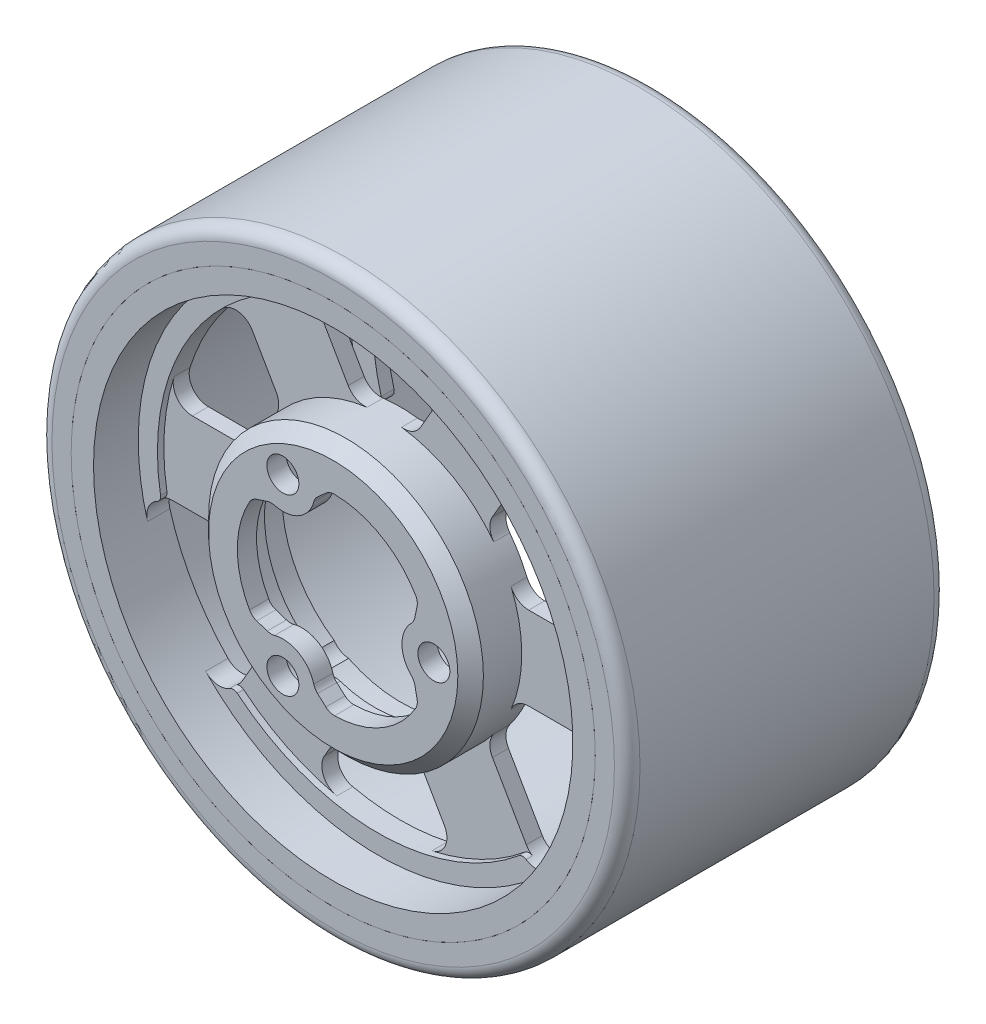
SolidWorks part; units mm, degrees
material "6061 合金"
ref_plane "前视基准面" through (0, 0, 0) normal (0, 0, 1) x (1, 0, 0)
ref_plane "上视基准面" through (0, 0, 0) normal (0, 1, 0) x (1, 0, 0)
ref_plane "右视基准面" through (0, 0, 0) normal (1, 0, 0) x (0, 0, -1)
sketch "草图1" plane through (0, 0, 0) normal (1, 0, 0) x (0, 0, -1)
  line L0 (0, 41) -> (-50, 41)
  line L6 (0, 71.4477) -> (0, 0) construction
  line L7 (0, 0) -> (-85.6485, 0) construction
  line L13 (0, 41) -> (0, 39)
  line L15 (-47, 9) -> (-50, 9)
  line L32 (-43.5, 18.5) -> (-43.5, 17.25)
  line L39 (-39.5, 39) -> (0, 39)
  line L43 (-39.5, 39) -> (-39.5, 18.5)
  line L44 (-50, 9) -> (-50, 21.5)
  line L46 (-43, 37.5) -> (-50, 37.5)
  line L52 (-42, 34.5) -> (-42, 21.5)
  line L53 (-43, 37.5) -> (-43, 34.5)
  line L54 (-43, 34.5) -> (-42, 34.5)
  line L57 (-43.5, 17.25) -> (-47, 17.25)
  line L58 (-47, 17.25) -> (-47, 9)
  line L59 (-39.5, 18.5) -> (-43.5, 18.5)
  line L60 (-42, 21.5) -> (-50, 21.5)
  line L61 (-50, 41) -> (-50, 37.5)
  dimension "D1" = 82
  dimension "D3" = 50
  dimension "D4" = 7
  dimension "D5" = 75
  dimension "D6" = 3
  dimension "D7" = 2.5
  dimension "D8" = 37
  dimension "D9" = 3
  dimension "D11" = 18
  dimension "D14" = 4
  dimension "D16" = 1.25
  dimension "D17" = 3.5
  dimension "D18" = 39
  dimension "D19" = 3
  dimension "D20" = 1
revolve "旋转1" add sketch "草图1" angle 360 about L7
sketch "草图15" plane through (0, 0, 0) normal (0, 1, 0) x (1, 0, 0)
  line L0 (0, 0) -> (50.0211, 0) construction
  line L1 (38.1, -6.35) -> (35.5, -6.35)
  line L2 (38.1, -6.35) -> (38.1, -8.35) construction
  line L3 (38.1, -8.35) -> (35.5, -8.35)
  line L4 (35.5, -6.35) -> (35.5, -8.35)
  line L5 (0, 0) -> (0, 24.19) construction
  line L6 (38.1, -8.35) -> (39, -8.35)
  line L7 (39, -8.35) -> (39, 0)
  line L8 (39, 0) -> (38.1, 0)
  line L9 (38.1, 0) -> (38.1, -6.35)
  dimension "D1" = 78
  dimension "D2" = 76.2
  dimension "D3" = 6.35
  dimension "D4" = 2
  dimension "D5" = 71
revolve "旋转2" add sketch "草图15" angle 360 about L5
sketch "草图16" plane through (0, 0, 50) normal (0, 0, 1) x (1, 0, 0)
  circle A0 centre (0, 0) radius 15.75 construction
  circle A1 centre (15.75, 0) radius 2.5
  circle A2 centre (-7.875, -13.6399) radius 2.5
  circle A3 centre (-7.875, 13.6399) radius 2.5
  point P12 (0, 0)
  dimension "D1" = 31.5
  dimension "D2" = 5
extrude "切除-拉伸1" cut sketch "草图16" against normal blind 10
sketch "草图18" plane through (0, 0, 42) normal (0, 0, 1) x (1, 0, 0)
  line L0 (-29.298, 5.166) -> (0, 0) construction
  arc A0 (-29.298, 5.166) -> (-27.9559, 10.1751) centre (0, 0) cw construction
  arc A1 (-32.4194, 11.7997) -> (-33.9759, 5.9909) centre (0, 0) ccw
  arc A2 (-23.4923, 8.5505) -> (-24.6202, 4.3412) centre (0, 0) ccw
  arc A3 (-23.4923, 8.5505) -> (-32.4194, 11.7997) centre (-27.9559, 10.1751) ccw
  arc A4 (-33.9759, 5.9909) -> (-24.6202, 4.3412) centre (-29.298, 5.166) ccw
  arc A5 (-19.1229, 22.7898) -> (-14.875, 25.7643) centre (0, 0) cw construction
  arc A6 (-17.25, 29.8779) -> (-22.1762, 26.4285) centre (0, 0) ccw
  arc A7 (-12.5, 21.6506) -> (-16.0697, 19.1511) centre (0, 0) ccw
  arc A8 (-12.5, 21.6506) -> (-17.25, 29.8779) centre (-14.875, 25.7643) ccw
  arc A9 (-22.1762, 26.4285) -> (-16.0697, 19.1511) centre (-19.1229, 22.7898) ccw
  arc A10 (0, 29.75) -> (5.166, 29.298) centre (0, 0) cw construction
  arc A11 (5.9909, 33.9759) -> (0, 34.5) centre (0, 0) ccw
  arc A12 (4.3412, 24.6202) -> (0, 25) centre (0, 0) ccw
  arc A13 (4.3412, 24.6202) -> (5.9909, 33.9759) centre (5.166, 29.298) ccw
  arc A14 (0, 34.5) -> (0, 25) centre (0, 29.75) ccw
  arc A15 (19.1229, 22.7898) -> (22.7898, 19.1229) centre (0, 0) cw construction
  arc A16 (26.4285, 22.1762) -> (22.1762, 26.4285) centre (0, 0) ccw
  arc A17 (19.1511, 16.0697) -> (16.0697, 19.1511) centre (0, 0) ccw
  arc A18 (19.1511, 16.0697) -> (26.4285, 22.1762) centre (22.7898, 19.1229) ccw
  arc A19 (22.1762, 26.4285) -> (16.0697, 19.1511) centre (19.1229, 22.7898) ccw
  arc A20 (29.298, 5.166) -> (29.75, 0) centre (0, 0) cw construction
  arc A21 (34.5, 0) -> (33.9759, 5.9909) centre (0, 0) ccw
  arc A22 (25, 0) -> (24.6202, 4.3412) centre (0, 0) ccw
  arc A23 (25, 0) -> (34.5, 0) centre (29.75, 0) ccw
  arc A24 (33.9759, 5.9909) -> (24.6202, 4.3412) centre (29.298, 5.166) ccw
  arc A25 (25.7643, -14.875) -> (22.7898, -19.1229) centre (0, 0) cw construction
  arc A26 (26.4285, -22.1762) -> (29.8779, -17.25) centre (0, 0) ccw
  arc A27 (19.1511, -16.0697) -> (21.6506, -12.5) centre (0, 0) ccw
  arc A28 (19.1511, -16.0697) -> (26.4285, -22.1762) centre (22.7898, -19.1229) ccw
  arc A29 (29.8779, -17.25) -> (21.6506, -12.5) centre (25.7643, -14.875) ccw
  arc A30 (10.1751, -27.9559) -> (5.166, -29.298) centre (0, 0) cw construction
  arc A31 (5.9909, -33.9759) -> (11.7997, -32.4194) centre (0, 0) ccw
  arc A32 (4.3412, -24.6202) -> (8.5505, -23.4923) centre (0, 0) ccw
  arc A33 (4.3412, -24.6202) -> (5.9909, -33.9759) centre (5.166, -29.298) ccw
  arc A34 (11.7997, -32.4194) -> (8.5505, -23.4923) centre (10.1751, -27.9559) ccw
  arc A35 (-10.1751, -27.9559) -> (-14.875, -25.7643) centre (0, 0) cw construction
  arc A36 (-17.25, -29.8779) -> (-11.7997, -32.4194) centre (0, 0) ccw
  arc A37 (-12.5, -21.6506) -> (-8.5505, -23.4923) centre (0, 0) ccw
  arc A38 (-12.5, -21.6506) -> (-17.25, -29.8779) centre (-14.875, -25.7643) ccw
  arc A39 (-11.7997, -32.4194) -> (-8.5505, -23.4923) centre (-10.1751, -27.9559) ccw
  arc A40 (-25.7643, -14.875) -> (-27.9559, -10.1751) centre (0, 0) cw construction
  arc A41 (-32.4194, -11.7997) -> (-29.8779, -17.25) centre (0, 0) ccw
  arc A42 (-23.4923, -8.5505) -> (-21.6506, -12.5) centre (0, 0) ccw
  arc A43 (-23.4923, -8.5505) -> (-32.4194, -11.7997) centre (-27.9559, -10.1751) ccw
  arc A44 (-29.8779, -17.25) -> (-21.6506, -12.5) centre (-25.7643, -14.875) ccw
  point P4 (-28.7363, 7.6999)
  point P15 (-17.0639, 24.3698)
  point P22 (2.5929, 29.6368)
  point P29 (21.0364, 21.0364)
  point P36 (29.6368, 2.5929)
  point P43 (24.3698, -17.0639)
  point P48 (0, 0)
  point P49 (7.6999, -28.7363)
  point P56 (-12.5729, -26.9627)
  point P63 (-26.9627, -12.5729)
  dimension "D1" = 25
  dimension "D2" = 34.5
  dimension "D3" = 10
  dimension "D4" = 9
extrude "切除-拉伸3" [suppressed] cut sketch "草图18" against normal blind 10
sketch "草图19" plane through (0, 0, 50) normal (0, 0, 1) x (1, 0, 0)
  line L0 (-17, 0) -> (0, 0) construction
  arc A0 (-16.4207, -4.3999) -> (-16.4207, 4.3999) centre (0, 0) cw construction
  arc A1 (-20.2844, 5.4352) -> (-20.2844, -5.4352) centre (0, 0) ccw
  arc A2 (-12.557, 3.3646) -> (-12.557, -3.3646) centre (0, 0) ccw
  arc A3 (-12.557, 3.3646) -> (-20.2844, 5.4352) centre (-16.4207, 4.3999) ccw
  arc A4 (-20.2844, -5.4352) -> (-12.557, -3.3646) centre (-16.4207, -4.3999) ccw
  arc A5 (4.3999, 16.4207) -> (12.0208, 12.0208) centre (0, 0) cw construction
  arc A6 (14.8492, 14.8492) -> (5.4352, 20.2844) centre (0, 0) ccw
  arc A7 (9.1924, 9.1924) -> (3.3646, 12.557) centre (0, 0) ccw
  arc A8 (9.1924, 9.1924) -> (14.8492, 14.8492) centre (12.0208, 12.0208) ccw
  arc A9 (5.4352, 20.2844) -> (3.3646, 12.557) centre (4.3999, 16.4207) ccw
  arc A10 (12.0208, -12.0208) -> (4.3999, -16.4207) centre (0, 0) cw construction
  arc A11 (5.4352, -20.2844) -> (14.8492, -14.8492) centre (0, 0) ccw
  arc A12 (3.3646, -12.557) -> (9.1924, -9.1924) centre (0, 0) ccw
  arc A13 (3.3646, -12.557) -> (5.4352, -20.2844) centre (4.3999, -16.4207) ccw
  arc A14 (14.8492, -14.8492) -> (9.1924, -9.1924) centre (12.0208, -12.0208) ccw
  point P4 (-17, 0)
  point P15 (8.5, 14.7224)
  point P22 (8.5, -14.7224)
  point P27 (0, 0)
  dimension "D1" = 17
  dimension "D2" = 4
  dimension "D3" = 30
  dimension "D4" = 3
extrude "切除-拉伸4" [suppressed] cut sketch "草图19" against normal blind 10
ref_plane "基准面1" through (0, 41, 0) normal (0, 1, 0) x (1, 0, 0)
ref_plane "基准面2" through (0, 0, 0) normal (0, -1, 0) x (-1, 0, 0)
sketch "草图21" plane through (0, 0, 47) normal (0, 0, -1) x (-1, 0, 0)
  circle A0 centre (7.875, 13.6399) radius 3
  circle A7 centre (7.875, -13.6399) radius 3
  circle A8 centre (-15.75, 0) radius 3
  point P9 (0, 0)
  dimension "D1" = 6
extrude "切除-拉伸5" cut sketch "草图21" along normal through all
fillet "圆角1" radius 2 6 edges at (-6.1705, 16.1086, 45.25) (-10.8652, 13.3981, 45.25) (-10.8652, -13.3981, 45.25) (-6.1705, -16.1086, 45.25) (17.0357, 2.7105, 45.25) (17.0357, -2.7105, 45.25)
sketch "草图23" plane through (0, 0, 47) normal (0, 0, -1) x (-1, 0, 0)
  arc A0 (-14.2242, -4.7615) -> (-14.2242, 4.7615) centre (-15.75, 0) ccw
  arc A1 (2.9885, 14.6993) -> (-14.2242, 4.7615) centre (0, 0) ccw
  arc A2 (2.9885, 14.6993) -> (11.2357, 9.9378) centre (7.875, 13.6399) ccw
  arc A3 (11.2357, -9.9378) -> (2.9885, -14.6993) centre (7.875, -13.6399) ccw
  arc A4 (-14.2242, -4.7615) -> (2.9885, -14.6993) centre (0, 0) ccw
  arc A5 (11.2357, -9.9378) -> (11.2357, 9.9378) centre (0, 0) ccw
  point P12 (0, 0)
  dimension "D1" = 30
  dimension "D2" = 10
  dimension "D3" = 3
extrude "切除-拉伸6" cut sketch "草图23" against normal through all
chamfer "倒角1" distance 2.5 6 edges at (-2.9885, 14.6993, 48.5) (-11.2357, 9.9378, 48.5) (-11.2357, -9.9378, 48.5) (-2.9885, -14.6993, 48.5) (14.2242, -4.7615, 48.5) (14.2242, 4.7615, 48.5)
fillet "圆角2" radius 2 12 edges at (-0.5879, -14.9885, 48.5) (-2.9313, -12.8917, 48.5) (-9.6989, -8.9844, 48.5) (-12.6865, -8.0034, 48.5) (-9.6989, 8.9844, 48.5) (-2.9313, 12.8917, 48.5) (-0.5879, 14.9885, 48.5) (13.2743, 6.9851, 48.5) (12.6302, 3.9073, 48.5) (12.6302, -3.9073, 48.5) (13.2743, -6.9851, 48.5) (-12.6865, 8.0034, 48.5)
sketch "草图25" plane through (0, 0, 42) normal (0, 0, 1) x (1, 0, 0)
  line L0 (0, 0) -> (41, 0) construction
  line L1 (0, 0) -> (-20.5, 35.507) construction
  line L2 (20.4939, 6.5) -> (33.8821, 6.5)
  line L3 (-11.3119, 32.5928) -> (-4.6178, 20.9982)
  line L4 (11.3119, 32.5928) -> (4.6178, 20.9982)
  line L5 (0, 0) -> (18.75, 32.476) construction
  line L6 (22.5702, 26.0928) -> (15.8761, 14.4982)
  line L7 (33.8821, -6.5) -> (20.4939, -6.5)
  line L8 (22.5702, -26.0928) -> (15.8761, -14.4982)
  line L9 (11.3119, -32.5928) -> (4.6178, -20.9982)
  line L10 (-4.6178, -20.9982) -> (-11.3119, -32.5928)
  line L11 (-22.5702, -26.0928) -> (-15.8761, -14.4982)
  line L12 (-33.8821, -6.5) -> (-20.4939, -6.5)
  line L13 (-33.8821, 6.5) -> (-20.4939, 6.5)
  line L14 (-15.8761, 14.4982) -> (-22.5702, 26.0928)
  circle A0 centre (0, 0) radius 41 construction
  circle A1 centre (0, 0) radius 21.5 construction
  circle A2 centre (0, 0) radius 37.5 construction
  arc A3 (11.3119, 32.5928) -> (-11.3119, 32.5928) centre (0, 0) ccw
  circle A4 centre (0, 0) radius 21.5 construction
  circle A5 centre (0, 0) radius 34.5 construction
  circle A6 centre (0, 0) radius 34.5 construction
  circle A7 centre (0, 0) radius 34.5
  arc A8 (33.8821, 6.5) -> (22.5702, 26.0928) centre (0, 0) ccw
  circle A9 centre (0, 0) radius 21.5
  arc A10 (20.4939, 6.5) -> (15.8761, 14.4982) centre (0, 0) ccw
  arc A11 (4.6178, 20.9982) -> (-4.6178, 20.9982) centre (0, 0) ccw
  arc A12 (15.8761, -14.4982) -> (20.4939, -6.5) centre (0, 0) ccw
  arc A13 (22.5702, -26.0928) -> (33.8821, -6.5) centre (0, 0) ccw
  arc A14 (-11.3119, -32.5928) -> (11.3119, -32.5928) centre (0, 0) ccw
  arc A15 (-4.6178, -20.9982) -> (4.6178, -20.9982) centre (0, 0) ccw
  arc A16 (-20.4939, -6.5) -> (-15.8761, -14.4982) centre (0, 0) ccw
  arc A17 (-33.8821, -6.5) -> (-22.5702, -26.0928) centre (0, 0) ccw
  arc A18 (-22.5702, 26.0928) -> (-33.8821, 6.5) centre (0, 0) ccw
  arc A19 (-15.8761, 14.4982) -> (-20.4939, 6.5) centre (0, 0) ccw
  point P47 (0, 0)
  dimension "D1" = 120
  dimension "D2" = 3
  dimension "D3" = 6.5
  dimension "D4" = 13
  dimension "D5" = 6.5
  dimension "D8" = 9.2356
  dimension "D9" = 6.5
  dimension "D6" = 0
  dimension "D7" = 0
extrude "切除-拉伸7" cut sketch "草图25" against normal blind 10
chamfer "倒角2" distance 2 angle 45 1 edges at (-21.5, 0, 50)
sketch "草图26" plane through (0, 0, 0) normal (1, 0, 0) x (0, 0, -1)
  line L0 (0, -38.1) -> (0, 38.1) construction
  line L1 (0, -2.5) -> (-50, -2.5)
  line L2 (0, -2.5) -> (0, 2.5)
  line L3 (0, 2.5) -> (-50, 2.5)
  line L4 (-50, -2.5) -> (-50, 2.5)
  line L5 (-50, 41) -> (-50, -41) construction
  dimension "D1" = 5
  dimension "D2" = 2.5
split line "分割线1" [suppressed]
sketch "草图28" plane through (0, 0, 0) normal (0, 0, 1) x (1, 0, 0)
  circle A0 centre (0, 0) radius 41
  circle A1 centre (0, 0) radius 46
  circle A2 centre (0, 0) radius 41 construction
  dimension "D1" = 92
extrude "凸台-拉伸1" add sketch "草图28" along normal up to surface (50 mm away) separate body up to face at (-37.5, 0, 50)
fillet "圆角4" radius 2 2 edges at (46, 0, 50) (46, 0, 0)
ref_plane "基准面3" through (0, 0, 25) normal (0, 0, -1) x (-1, 0, 0)
sketch "草图29" plane through (0, 0, 6.35) normal (0, 0, -1) x (-1, 0, 0)
  line L0 (0, 0) -> (0, -50000) construction
  line L1 (0, 0) -> (-50000, 0) construction
  line L8 (-8.2463, 37.1969) -> (-7.6836, 34.6585)
  line L9 (8.2463, 37.1969) -> (7.6836, 34.6585)
  line L10 (36.3366, -11.4569) -> (33.857, -10.6751)
  line L11 (28.0903, -25.74) -> (26.1733, -23.9835)
  line L12 (-28.0903, -25.74) -> (-26.1733, -23.9835)
  line L13 (-36.3366, -11.4569) -> (-33.857, -10.6751)
  arc A0 (26.1733, -23.9835) -> (33.857, -10.6751) centre (0, 0) ccw
  arc A1 (28.0903, -25.74) -> (36.3366, -11.4569) centre (0, 0) ccw
  circle A8 centre (0, 0) radius 35.5 construction
  arc A11 (8.2463, 37.1969) -> (-8.2463, 37.1969) centre (0, 0) ccw
  arc A12 (7.6836, 34.6585) -> (-7.6836, 34.6585) centre (0, 0) ccw
  circle A13 centre (0, 0) radius 38.1 construction
  arc A14 (-33.857, -10.6751) -> (-26.1733, -23.9835) centre (0, 0) ccw
  arc A15 (-36.3366, -11.4569) -> (-28.0903, -25.74) centre (0, 0) ccw
  point P24 (0, 0)
  point P27 (0, 0)
  dimension "D2" = 3
  dimension "D1" = 25
extrude "切除-拉伸8" cut sketch "草图29" against normal blind 10
sketch "草图30" plane through (0, 0, 43) normal (0, 0, 1) x (1, 0, 0)
  line L0 (11.3119, 32.5928) -> (12.837, 35.2344)
  line L1 (4.6178, 20.9982) -> (11.3119, 32.5928) construction
  line L2 (0, 0) -> (0, 53.8837) construction
  line L3 (-11.3119, 32.5928) -> (-12.837, 35.2344)
  line L4 (33.8821, -6.5) -> (36.9324, -6.5)
  line L5 (22.5702, -26.0928) -> (24.0954, -28.7344)
  line L6 (-22.5702, -26.0928) -> (-24.0954, -28.7344)
  line L7 (-33.8821, -6.5) -> (-36.9324, -6.5)
  circle A0 centre (0, 0) radius 34.5 construction
  circle A1 centre (0, 0) radius 37.5
  arc A2 (12.837, 35.2344) -> (-12.837, 35.2344) centre (0, 0) ccw
  arc A3 (11.3119, 32.5928) -> (-11.3119, 32.5928) centre (0, 0) ccw
  arc A4 (24.0954, -28.7344) -> (36.9324, -6.5) centre (0, 0) ccw
  arc A5 (22.5702, -26.0928) -> (33.8821, -6.5) centre (0, 0) ccw
  arc A6 (-36.9324, -6.5) -> (-24.0954, -28.7344) centre (0, 0) ccw
  arc A7 (-33.8821, -6.5) -> (-22.5702, -26.0928) centre (0, 0) ccw
  point P22 (0, 0)
  dimension "D1" = 0
  dimension "D2" = 3
extrude "切除-拉伸9" cut sketch "草图30" against normal blind 5
fillet "圆角5" radius 3 36 edges at (-15.8761, 14.4982, 40.75) (-20.4939, 6.5, 40.75) (-33.8821, 6.5, 40.75) (-22.5702, 26.0928, 40.75) (15.8761, -14.4982, 40.75) (20.4939, -6.5, 40.75) (-4.6178, -20.9982, 40.75) (4.6178, -20.9982, 40.75) (11.3119, -32.5928, 40.75) (-11.3119, -32.5928, 40.75) (4.6178, 20.9982, 40.75) (-4.6178, 20.9982, 40.75) (-20.4939, -6.5, 40.75) (-15.8761, -14.4982, 40.75) (20.4939, 6.5, 40.75) (15.8761, 14.4982, 40.75) (22.5702, 26.0928, 40.75) (33.8821, 6.5, 40.75) (11.3119, 32.5928, 42.5) (-11.3119, 32.5928, 42.5) (-12.837, 35.2344, 41.25) (12.837, 35.2344, 41.25) (12.0745, 33.9136, 43) (-12.0745, 33.9136, 43) (22.5702, -26.0928, 42.5) (33.8821, -6.5, 42.5) (36.9324, -6.5, 41.25) (24.0954, -28.7344, 41.25) (23.3328, -27.4136, 43) (35.4073, -6.5, 43) (-33.8821, -6.5, 42.5) (-22.5702, -26.0928, 42.5) (-24.0954, -28.7344, 41.25) (-36.9324, -6.5, 41.25) (-35.4073, -6.5, 43) (-23.3328, -27.4136, 43)
fillet "圆角6" radius 1 6 edges at (-22.6339, -26.0376, 42.5) (22.6339, -26.0376, 42.5) (33.8662, -6.5828, 42.5) (11.2322, 32.6204, 42.5) (-11.2322, 32.6204, 42.5) (-33.8662, -6.5828, 42.5)
fillet "圆角7" radius 1 12 edges at (-7.6836, 34.6585, 7.35) (-33.857, -10.6751, 7.35) (-28.0903, -25.74, 7.35) (-26.1733, -23.9835, 7.35) (26.1733, -23.9835, 7.35) (28.0903, -25.74, 7.35) (36.3366, -11.4569, 7.35) (33.857, -10.6751, 7.35) (7.6836, 34.6585, 7.35) (8.2463, 37.1969, 7.35) (-8.2463, 37.1969, 7.35) (-36.3366, -11.4569, 7.35)
